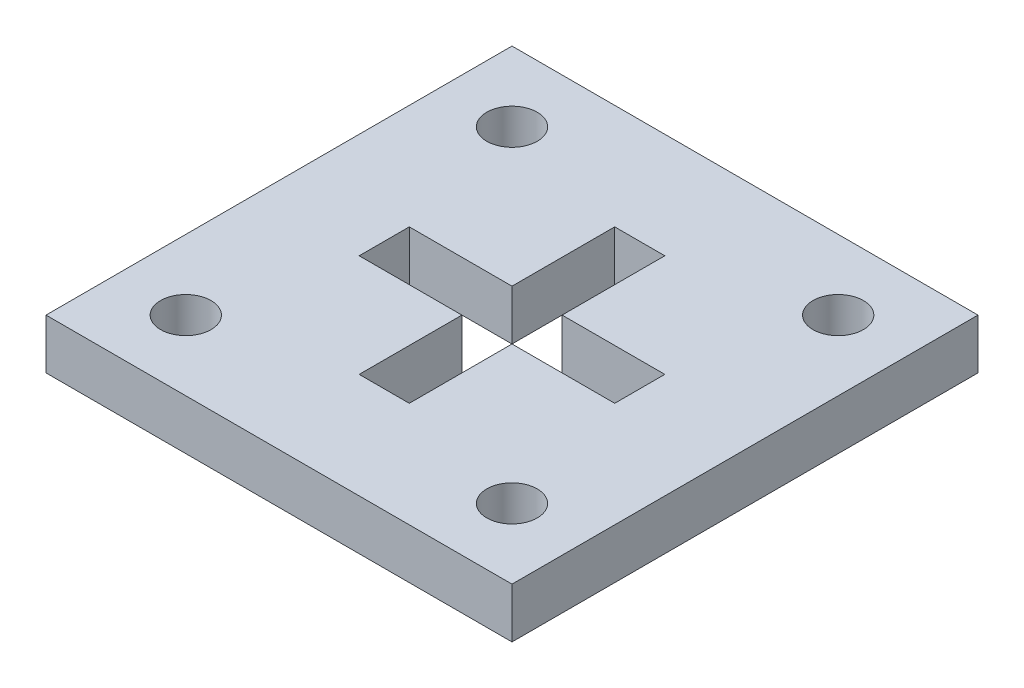
SolidWorks part; units mm, degrees
ref_plane "Front Plane" through (0, 0, 0) normal (0, 0, 1) x (1, 0, 0)
ref_plane "Top Plane" through (0, 0, 0) normal (0, 1, 0) x (1, 0, 0)
ref_plane "Right Plane" through (0, 0, 0) normal (1, 0, 0) x (0, 0, -1)
sketch "Sketch1" plane through (0, 0, 0) normal (0, 1, 0) x (1, 0, 0)
  line L1 (0, 0) -> (50.8, 0)
  line L2 (0, 0) -> (0, 50.8)
  line L3 (0, 50.8) -> (50.8, 50.8)
  line L4 (50.8, 0) -> (50.8, 50.8)
  line L5 (25.4, 50.8) -> (25.4, 0) construction
  line L6 (0, 25.4) -> (50.8, 25.4) construction
  point P80 (25.4, 25.4)
  dimension "D1" = 50.8
extrude "Boss-Extrude1" add sketch "Sketch1" along normal blind 5.461
sketch "Sketch2" plane through (0, 5.461, 0) normal (0, 1, 0) x (1, 0, 0)
  line L0 (11.4723, 50.8) -> (11.4723, 0) construction
  line L3 (50.8, 50.8) -> (0, 50.8) construction
  line L11 (0, 0) -> (50.8, 0) construction
  line L12 (0, 50.8) -> (0, 0) construction
  line L17 (0, 11.4723) -> (50.8, 11.4723) construction
  line L18 (50.8, 0) -> (50.8, 50.8) construction
  line L22 (39.3277, 50.8) -> (39.3277, 0) construction
  line L23 (0, 39.3277) -> (50.8, 39.3277) construction
  line L24 (25.4, 39.3277) -> (25.4, 11.4723) construction
  line L25 (11.4723, 25.4) -> (39.3277, 25.4) construction
  line L26 (28.1305, 28.1305) -> (39.3277, 28.1305)
  line L27 (22.6695, 39.3277) -> (28.1305, 39.3277)
  line L28 (22.6695, 39.3277) -> (22.6695, 28.1305)
  line L29 (22.6695, 11.4723) -> (28.1305, 11.4723)
  line L30 (28.1305, 39.3277) -> (28.1305, 28.1305)
  line L31 (25.4, 11.4723) -> (25.4, 39.3277) construction
  line L32 (22.225, 25.4) -> (28.575, 25.4) construction
  line L33 (11.4723, 28.1305) -> (22.6695, 28.1305)
  line L34 (11.4723, 28.1305) -> (11.4723, 22.6695)
  line L35 (11.4723, 22.6695) -> (22.6695, 22.6695)
  line L36 (39.3277, 28.1305) -> (39.3277, 22.6695)
  line L37 (25.4, 22.225) -> (25.4, 28.575) construction
  line L38 (11.4723, 25.4) -> (39.3277, 25.4) construction
  line L39 (28.1305, 22.6695) -> (39.3277, 22.6695)
  line L40 (28.1305, 22.6695) -> (28.1305, 11.4723)
  line L41 (22.6695, 22.6695) -> (22.6695, 11.4723)
  point P240 (25.4, 25.4)
  point P531 (25.4, 25.4)
  dimension "D1" = 11.4723
  dimension "D2" = 11.4723
  dimension "D3" = 11.4723
  dimension "D4" = 11.4723
  dimension "D5" = 5.461
  dimension "D6" = 5.461
extrude "Cut-Extrude1" cut sketch "Sketch2" against normal blind 5.461
sketch "Sketch5" plane through (0, 5.461, 0) normal (0, 1, 0) x (1, 0, 0)
  line L0 (7.62, 43.18) -> (7.62, 7.62) construction
  line L1 (0, 50.8) -> (50.8, 50.8) construction
  line L2 (0, 50.8) -> (0, 0) construction
  line L3 (0, 0) -> (50.8, 0) construction
  line L4 (50.8, 50.8) -> (50.8, 0) construction
  line L5 (7.62, 7.62) -> (43.18, 7.62) construction
  line L6 (43.18, 43.18) -> (43.18, 7.62) construction
  line L7 (7.62, 43.18) -> (43.18, 43.18) construction
  dimension "D1" = 7.62
hole_wizard "M5 Clearance Hole1" positions "Sketch6" profile "Sketch8" hole size "M5" standard "ANSI Metric" end condition through all
sketch "Sketch6" plane through (0, 5.461, 0) normal (0, 1, 0) x (1, 0, 0)
  point P0 (7.62, 43.18)
  point P3 (43.18, 43.18)
  point P6 (43.18, 7.62)
  point P9 (7.62, 7.62)
sketch "Sketch8" plane through (7.62, 5.461, -43.18) normal (1, 0, 0) x (0, 0, 1)
  line L0 (0, 0) -> (0, 5.461)
  line L1 (0, 5.461) -> (2.75, 5.461)
  line L2 (2.75, 5.461) -> (2.75, 0)
  line L5 (2.75, 0) -> (0, 0)
  line L11 (0, -6.35) -> (0, 107.95) construction
  dimension "Thru Hole Dia." = 5.5
  dimension "Thru Hole Depth" = 5.461
equation "\"Stock Thickness\"= .215in"
equation "\"D1@Boss-Extrude1\"=\"Stock Thickness\""
equation "\"D1@Cut-Extrude1\"=\"Stock Thickness\""
equation "\"D1@Sketch2\"=\"D1@Sketch1\"/3 - \"Stock Thickness\""
equation "\"D2@Sketch2\"=\"D1@Sketch1\"/3 - \"Stock Thickness\""
equation "\"D3@Sketch2\"=\"D2@Sketch2\""
equation "\"D4@Sketch2\"=\"D1@Sketch2\""
equation "\"D5@Sketch2\"=\"Stock Thickness\""
equation "\"D6@Sketch2\"=\"Stock Thickness\""
